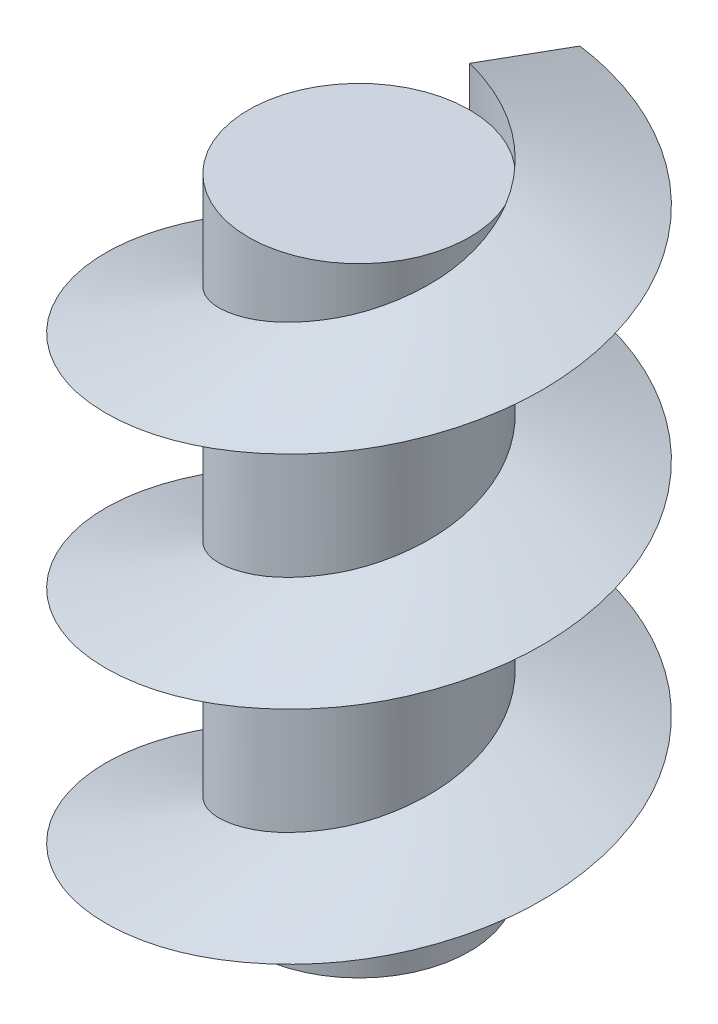
SolidWorks part; units mm, degrees
ref_plane "Face" through (0, 0, 0) normal (0, 0, 1) x (1, 0, 0)
ref_plane "Dessus" through (0, 0, 0) normal (0, 1, 0) x (1, 0, 0)
ref_plane "Droite" through (0, 0, 0) normal (1, 0, 0) x (0, 0, -1)
sketch "Esquisse2" plane through (0, 4.6576, 0) normal (0, -1, 0) x (1, 0, 0)
  circle A0 centre (-0.3894, -13.48) radius 1.25
  dimension "D1" = 2.5
extrude "Extrusion1" add sketch "Esquisse2" along normal blind 10
sketch "Esquisse3" plane through (0, -5.3424, 0) normal (0, -1, 0) x (1, 0, 0)
  circle A0 centre (-0.3894, -13.48) radius 2.5
  dimension "D1" = 5
curve "Hélice/Spirale1" pitch 2.5 height 10 radius 2.5 centre (-0.3894, -5.3424, -13.48) axis (0, 1, 0) start towards (0, 0, -1)
ref_plane "Plan1" through (-0.3894, 0, 0) normal (-1, 0, 0) x (0, 0, 1)
sketch "Esquisse4" plane through (-0.3894, 0, 0) normal (-1, 0, 0) x (0, 0, 1)
  line L0 (-15.98, -5.3424) -> (-14.73, -4.8875)
  line L1 (-14.73, 4.6576) -> (-14.73, -5.3424) construction
  line L2 (-15.98, -5.3424) -> (-14.73, -5.7974)
  line L3 (-14.73, -4.8875) -> (-14.73, -5.7974)
  line L4 (-14.73, -5.3424) -> (-12.23, -5.3424) construction
  spline S3 degree 3 poles (-15.98, -5.3424) (-15.98, -5.2907) (-15.8498, -5.186) (-15.2938, -5.03) (-14.4616, -4.8737) (-13.48, -4.7174) (-12.4984, -4.5612) (-11.6662, -4.4049) (-11.1102, -4.2487) (-10.9149, -4.0924) (-11.1102, -3.9362) (-11.6662, -3.7799) (-12.4984, -3.6237) (-13.48, -3.4674) (-14.4616, -3.3112) (-15.2938, -3.1549) (-15.8498, -2.9987) (-16.0451, -2.8424) (-15.8498, -2.6862) (-15.2938, -2.5299) (-14.4616, -2.3737) (-13.48, -2.2174) (-12.4984, -2.0612) (-11.6662, -1.9049) (-11.1102, -1.7487) (-10.9149, -1.5924) (-11.1102, -1.4362) (-11.6662, -1.2799) (-12.4984, -1.1237) (-13.48, -0.9674) (-14.4616, -0.8112) (-15.2938, -0.6549) (-15.8498, -0.4987) (-16.0451, -0.3424) (-15.8498, -0.1862) (-15.2938, -0.0299) (-14.4616, 0.1263) (-13.48, 0.2826) (-12.4984, 0.4388) (-11.6662, 0.5951) (-11.1102, 0.7513) (-10.9149, 0.9076) (-11.1102, 1.0638) (-11.6662, 1.2201) (-12.4984, 1.3763) (-13.48, 1.5326) (-14.4616, 1.6888) (-15.2938, 1.8451) (-15.8498, 2.0013) (-16.0451, 2.1576) (-15.8498, 2.3138) (-15.2938, 2.4701) (-14.4616, 2.6263) (-13.48, 2.7826) (-12.4984, 2.9388) (-11.6662, 3.0951) (-11.1102, 3.2513) (-10.9149, 3.4076) (-11.1102, 3.5638) (-11.6662, 3.7201) (-12.4984, 3.8763) (-13.48, 4.0326) (-14.4616, 4.1888) (-15.2938, 4.3451) (-15.8498, 4.5012) (-15.98, 4.6058) (-15.98, 4.6576) knots 0 0 0 0 0.015625 0.03125 0.046875 0.0625 0.078125 0.09375 0.109375 0.125 0.140625 0.15625 0.171875 0.1875 0.203125 0.21875 0.234375 0.25 0.265625 0.28125 0.296875 0.3125 0.328125 0.34375 0.359375 0.375 0.390625 0.40625 0.421875 0.4375 0.453125 0.46875 0.484375 0.5 0.515625 0.53125 0.546875 0.5625 0.578125 0.59375 0.609375 0.625 0.640625 0.65625 0.671875 0.6875 0.703125 0.71875 0.734375 0.75 0.765625 0.78125 0.796875 0.8125 0.828125 0.84375 0.859375 0.875 0.890625 0.90625 0.921875 0.9375 0.953125 0.96875 0.984375 1 1 1 1 construction
  dimension "D1" = 40
  dimension "D2" = 20
sweep "Balayage1" add profiles "Esquisse4" path "Hélice/Spirale1"
sketch "Esquisse5" plane through (0, -5.3424, 0) normal (0, -1, 0) x (1, 0, 0)
  circle A0 centre (-0.3894, -13.48) radius 3.6154
extrude "Extrusion2" cut sketch "Esquisse5" against normal blind 3 and the other way through all
